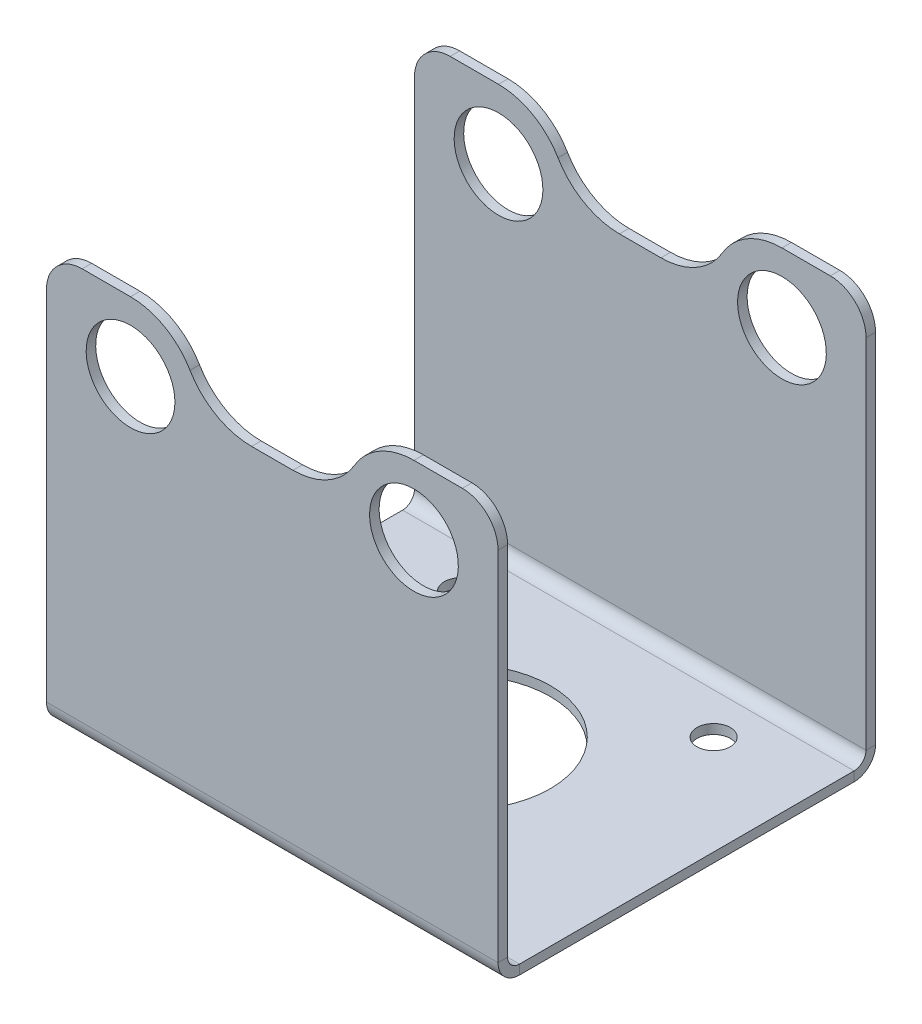
SolidWorks part; units mm, degrees
note: The reader was unsure of these and kept them because the rebuilt part matched: thickness of "Base-Flange1", "Edge-Flange1", "Sheet-Metal1", "Sheet-Metal2", "Sheet-Metal3", "Sheet-Metal11"; flange length of "Edge-Flange1".
material "Brass"
ref_plane "Front Plane" through (0, 0, 0) normal (0, 0, 1) x (1, 0, 0)
ref_plane "Top Plane" through (0, 0, 0) normal (0, 1, 0) x (1, 0, 0)
ref_plane "Right Plane" through (0, 0, 0) normal (1, 0, 0) x (0, 0, -1)
sketch "Sketch1" plane through (0, 0, 0) normal (0, 1, 0) x (1, 0, 0)
  line L0 (-24.0792, 19.1135) -> (24.0792, 19.1135)
  line L1 (24.0792, 19.1135) -> (24.0792, -19.1135)
  line L2 (24.0792, -19.1135) -> (-24.0792, -19.1135)
  line L3 (-24.0792, -19.1135) -> (-24.0792, 19.1135)
  line L4 (-24.0792, -19.1135) -> (24.0792, 19.1135) construction
  line L5 (0, 0) -> (13.4704, 13.4704) construction
  line L6 (0, 0) -> (13.4704, -13.4704) construction
  line L7 (0, 0) -> (0, 19.1135) construction
  line L8 (0, 0) -> (-13.4704, -13.4704) construction
  line L9 (0, 0) -> (-13.4704, 13.4704) construction
  circle A0 centre (0, 0) radius 9.525
  circle A1 centre (13.4704, -13.4704) radius 1.778
  circle A2 centre (13.4704, 13.4704) radius 1.778
  circle A3 centre (-13.4704, 13.4704) radius 1.778
  circle A4 centre (-13.4704, -13.4704) radius 1.778
  point P5 (0, 0)
  dimension "D3" = 19.05
  dimension "D4" = 90
  dimension "D5" = 45
  dimension "D6" = 19.05
  dimension "D8" = 3.556
  dimension "D9" = 3.556
  dimension "D1" = 38.227
  dimension "D2" = 48.1584
  dimension "D7" = 19.05
base flange "Base-Flange1" sketch "Sketch1" thickness 1.016 reverse thickness direction no parameters "D1"=1.27
edge flange "Edge-Flange1" sketch "Sketch10" flange angle 90 flange length 45.7962 flange position material outside bend radius 1.27 thickness 1.016 relief rectangular parameters "D6"=10
sketch "Sketch10" plane through (0, 0, -19.1135) normal (0, 0, -1) x (-1, 0, 0)
  line L0 (-24.0792, 0) -> (24.0792, 0) construction
  line L1 (-24.0792, 0) -> (24.0792, 0)
  line L2 (-24.0792, 0) -> (-24.0792, 44.7802)
  line L3 (-24.0792, 44.7802) -> (24.0792, 44.7802)
  line L4 (24.0792, 44.7802) -> (24.0792, 0)
  line L5 (-24.0792, -1.016) -> (24.0792, -1.016) construction
  line L6 (15.113, 35.814) -> (-15.113, 35.814) construction
  circle A0 centre (-15.113, 35.814) radius 4.7308
  circle A1 centre (15.113, 35.814) radius 4.7308
  dimension "D2" = 8.9662
  dimension "D3" = 9.4615
  dimension "D1" = 36.83
  dimension "D4" = 30.226
  dimension "D5" = 8.9662
  dimension "D6" = 8.9662
  dimension "D7" = 8.9662
bend "EdgeBend1" bend radius 1.27 bend angle 90 parameters "D5"=1
mirror "Mirror1" about plane through (0, 0, 0) normal (0, 0, 1) of "Edge-Flange1"
bend "MirrorBend1" bend radius 1.27 bend angle 90 parameters "D5"=2
sketch "Sketch11" plane through (0, 0, -20.1295) normal (0, 0, -1) x (-1, 0, 0)
  line L2 (24.0792, 44.7802) -> (-24.0792, 44.7802)
  line L5 (7.747, 35.814) -> (-7.747, 35.814)
  line L12 (-15.113, 43.18) -> (-24.0792, 43.18)
  line L13 (-24.0792, 44.7802) -> (-24.0792, 1.27) construction
  line L14 (-24.0792, 43.18) -> (-24.0792, 44.7802)
  line L15 (15.113, 43.18) -> (24.0792, 43.18)
  line L16 (24.0792, 1.27) -> (24.0792, 44.7802) construction
  line L17 (24.0792, 43.18) -> (24.0792, 44.7802)
  circle A2 centre (15.113, 35.814) radius 7.366
  circle A3 centre (-15.113, 35.814) radius 7.366
  dimension "D1" = 14.732
extrude "Cut-Extrude7" cut sketch "Sketch11" against normal through all
fillet "Fillet2" radius 7.62 4 edges at (7.747, 35.814, -19.6215) (-7.747, 35.814, -19.6215) (-7.747, 35.814, 19.6215) (7.747, 35.814, 19.6215)
fillet "Fillet3" radius 3.81 4 edges at (24.0792, 43.18, 19.6215) (-24.0792, 43.18, 19.6215) (-24.0792, 43.18, -19.6215) (24.0792, 43.18, -19.6215)
unfold "Unfold1" [suppressed]
sketch "Sketch11-2" plane through (0, -1.016, -19.3664) normal (0, -1, 0) x (-1, 0, 0)
  line L2 (24.0792, 44.7802) -> (-24.0792, 44.7802)
  line L5 (7.747, 35.814) -> (-7.747, 35.814)
  line L12 (-15.113, 43.18) -> (-24.0792, 43.18)
  line L14 (-24.0792, 43.18) -> (-24.0792, 44.7802)
  line L15 (15.113, 43.18) -> (24.0792, 43.18)
  line L17 (24.0792, 43.18) -> (24.0792, 44.7802)
  circle A2 centre (15.113, 35.814) radius 7.366
  circle A3 centre (-15.113, 35.814) radius 7.366
  dimension "D1" = 14.732
sketch "Bend-Lines1" [suppressed] plane through (0, 0, 0) normal (0, 1, 0) x (1, 0, 0)
sketch "Bounding-Box1" [suppressed] plane through (0, 0, 0) normal (0, 1, 0) x (1, 0, 0)
sheet metal parameters "Sheet-Metal1" thickness 1.016 parameters "D1"=1.27, "D7"=1.27
flat pattern "Flat-Pattern1"
sketch "Bend-Lines2" plane through (0, 0, 0) normal (0, 1, 0) x (1, 0, 0)
sketch3d "Bounding-Box2" [suppressed]
  line L0 (-23.495, 18.034, 0) -> (23.495, 18.034, 0) construction
  line L1 (-23.495, -18.034, 0) -> (23.495, -18.034, 0) construction
  line L2 (-23.495, 18.034, 0) -> (-23.495, -18.034, 0) construction
  line L3 (23.495, 18.034, 0) -> (23.495, -18.034, 0) construction
sheet metal parameters "Sheet-Metal2" thickness 1.016 parameters "D1"=1.27, "D7"=1.27
flat pattern "Flat-Pattern1"
sketch "Bend-Lines2" plane through (0, 0, 0) normal (0, 1, 0) x (1, 0, 0)
  line L0 (23.495, 18.2602) -> (-23.495, 18.2602) construction
  line L1 (23.495, 18.2602) -> (-23.495, 18.2602) construction
sketch3d "Bounding-Box2" [suppressed]
  line L0 (-23.495, -18.034, 0) -> (-23.495, 45.4104, 0) construction
  line L1 (23.495, -18.034, 0) -> (23.495, 45.4104, 0) construction
  line L2 (-23.495, -18.034, 0) -> (23.495, -18.034, 0) construction
  line L3 (-23.495, 45.4104, 0) -> (23.495, 45.4104, 0) construction
bend of the flat pattern "Flatten-<EdgeBend1>1"
sheet metal parameters "Sheet-Metal3" thickness 1.016 parameters "D1"=1.27, "D7"=1.27
flat pattern "Flat-Pattern1" [suppressed]
sketch "Bend-Lines2" plane through (0, 0, 0) normal (0, 1, 0) x (1, 0, 0)
  line L0 (24.0792, 19.5302) -> (-24.0792, 19.5302) construction
  line L1 (24.0792, 19.5302) -> (-24.0792, 19.5302) construction
  line L2 (-24.0792, -19.5302) -> (24.0792, -19.5302) construction
  line L3 (-24.0792, -19.5302) -> (24.0792, -19.5302) construction
sketch3d "Bounding-Box2" [suppressed]
  line L0 (-24.0792, -52.8526, 0) -> (-24.0792, 52.8526, 0) construction
  line L1 (24.0792, -52.8526, 0) -> (24.0792, 52.8526, 0) construction
  line L2 (-24.0792, -52.8526, 0) -> (24.0792, -52.8526, 0) construction
  line L3 (-24.0792, 52.8526, 0) -> (24.0792, 52.8526, 0) construction
bend of the flat pattern "Flatten-<EdgeBend1>1"
bend of the flat pattern "Flatten-<MirrorBend1>1"
sketch "Sketch11-1" plane through (0, -1.27, -19.7564) normal (0, -1, 0) x (-1, 0, 0)
  line L2 (24.0792, 24.13) -> (-24.0792, 24.13)
  line L4 (24.0663, 15.1638) -> (25.4769, 15.1638)
  line L5 (7.747, 15.1638) -> (-7.747, 15.1638)
  line L6 (25.4769, 15.1638) -> (25.4769, 24.13)
  line L7 (25.4769, 24.13) -> (24.0792, 24.13)
  line L8 (-24.0663, 15.1638) -> (-25.6537, 15.1638)
  line L9 (-25.6537, 15.1638) -> (-25.6537, 24.13)
  line L10 (-25.6537, 24.13) -> (-24.0792, 24.13)
  line L12 (24.0792, 1.27) -> (-24.0792, 1.27)
  circle A2 centre (15.113, 15.1638) radius 7.366
  circle A3 centre (-15.113, 15.1638) radius 7.366
  arc A4 (-15.113, 22.5298) -> (-24.0663, 15.1638) centre (-15.9067, 14.3701) ccw
  arc A5 (15.113, 22.5298) -> (24.0663, 15.1638) centre (15.9067, 14.3701) cw
  dimension "D1" = 14.732
  dimension "D3" = 8.1982
  dimension "D2" = 13.1001
sheet metal parameters "Sheet-Metal11" thickness 1.016 parameters "D1"=1.27, "D7"=1.27
flat pattern "Flat-Pattern1"
sketch "Bend-Lines2" plane through (0, 0, -20.1295) normal (0, 0, -1) x (-1, 0, 0)
  line L0 (24.0792, -0.1264) -> (-24.0792, -0.1264) construction
  line L1 (24.0792, -0.1264) -> (-24.0792, -0.1264) construction
  line L2 (24.0792, -38.6063) -> (-24.0792, -38.6063) construction
  line L3 (24.0792, -38.6063) -> (-24.0792, -38.6063) construction
sketch3d "Bounding-Box2" [suppressed]
  line L0 (-24.0793, 43.1799, 0) -> (-24.0792, -81.9128, 0) construction
  line L1 (24.0791, 43.18, 0) -> (24.0792, -81.9127, 0) construction
  line L2 (-24.0793, 43.1799, 0) -> (24.0791, 43.18, 0) construction
  line L3 (-24.0792, -81.9128, 0) -> (24.0792, -81.9127, 0) construction
bend of the flat pattern "Flatten-<MirrorBend1>1"
bend of the flat pattern "Flatten-<EdgeBend1>1"
